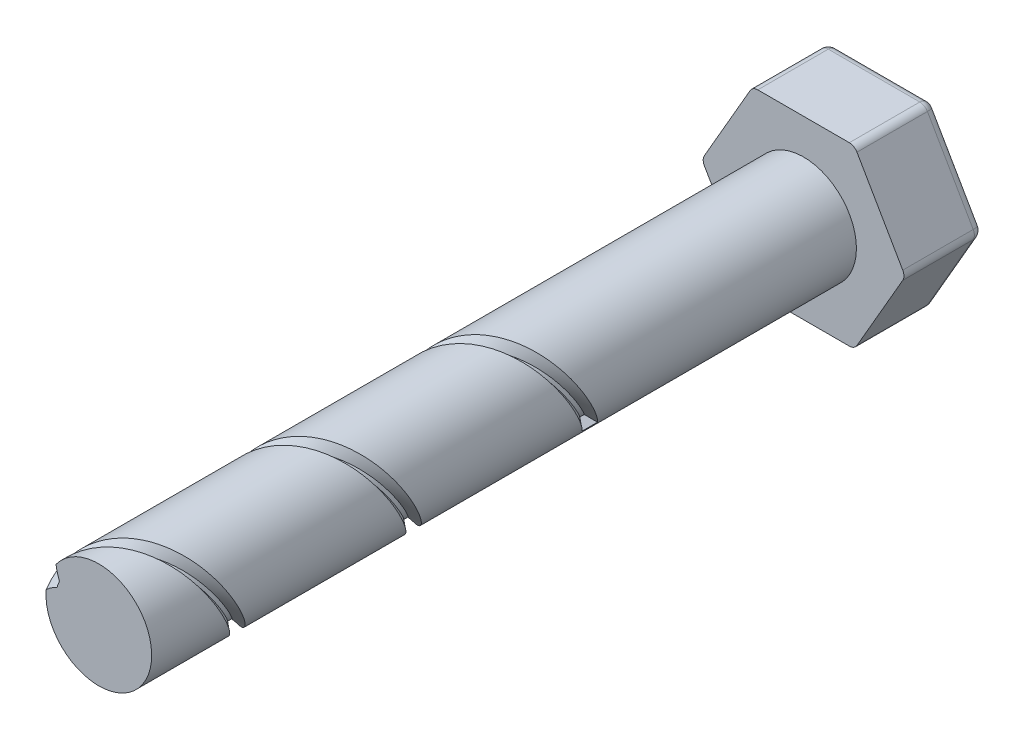
SolidWorks part; units mm, degrees
ref_plane "Front Plane" through (0, 0, 0) normal (0, 0, 1) x (1, 0, 0)
ref_plane "Top Plane" through (0, 0, 0) normal (0, 1, 0) x (1, 0, 0)
ref_plane "Right Plane" through (0, 0, 0) normal (1, 0, 0) x (0, 0, -1)
sketch "Sketch1" plane through (0, 0, 0) normal (0, 0, 1) x (1, 0, 0)
  circle A0 centre (0, 0) radius 3
  dimension "D1" = 6
extrude "Boss-Extrude1" add sketch "Sketch1" along normal blind 40
sketch "Sketch2" plane through (0, 0, 0) normal (0, 0, -1) x (-1, 0, 0)
  line L1 (5.7735, 0) -> (2.8868, 5)
  line L2 (2.8868, 5) -> (-2.8868, 5)
  line L3 (-2.8868, 5) -> (-5.7735, 0)
  line L4 (-5.7735, 0) -> (-2.8868, -5)
  line L5 (-2.8868, -5) -> (2.8868, -5)
  line L6 (2.8868, -5) -> (5.7735, 0)
  circle A0 centre (0, 0) radius 5 construction
  dimension "D1" = 10
extrude "Boss-Extrude2" add sketch "Sketch2" along normal blind 4.5
fillet "Fillet1" radius 0.5 12 edges at (0, -5, -4.5) (4.3301, -2.5, -4.5) (4.3301, 2.5, -4.5) (0, 5, -4.5) (-4.3301, 2.5, -4.5) (-4.3301, -2.5, -4.5) (-5.7735, 0, -2.25) (2.8868, 5, -2.25) (5.7735, 0, -2.25) (2.8868, -5, -2.25) (-2.8868, -5, -2.25) (-2.8868, 5, -2.25)
thread "Thread1" pitch 1 start angle 0, offset 1, length 25, pitch 10, diameter 6
ref_plane "Plane1" through (-3, 0, 41) normal (0, -1, 0) x (-1, 0, 0)
sketch "Thread Profile1" plane through (-3, 0, 41) normal (0, -1, 0) x (-1, 0, 0)
  line L0 (0, 0) -> (0, 1) construction
  line L11 (0, 0) -> (0, 0.875)
  line L12 (0, 0.875) -> (-0.5413, 0.5625)
  line L13 (-0.5413, 0.5625) -> (-0.5413, 0.3125)
  line L15 (-0.5413, 0.3125) -> (0, 0)
  line L17 (-0.5413, 0.4375) -> (0, 0.4375) construction
  point P2 (0, 0)
  dimension "Pitch" = 1
  dimension "Profile_Angle" = 60
  dimension "Profile_Land" = 0.25
  dimension "Profile_Height" = 0.5413
